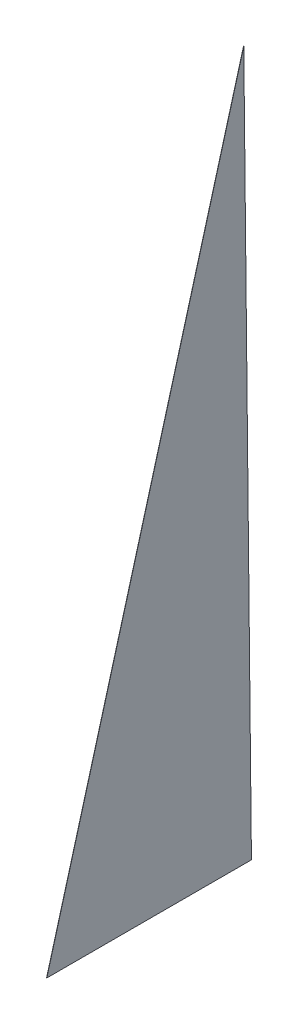
SolidWorks part; units mm, degrees
material "Corrugated Paper"
ref_plane "Front Plane" through (0, 0, 0) normal (0, 0, 1) x (1, 0, 0)
ref_plane "Top Plane" through (0, 0, 0) normal (0, 1, 0) x (1, 0, 0)
ref_plane "Right Plane" through (0, 0, 0) normal (1, 0, 0) x (0, 0, -1)
sketch "Sketch1" plane through (0, 0, 0) normal (1, 0, 0) x (0, 0, -1)
  line L0 (0, 0) -> (168.45, 605.88)
  line L1 (168.45, 605.88) -> (175, 0)
  line L2 (175, 0) -> (0, 0)
  point P6 (61.0733, 548.1905)
  dimension "D1" = 175
  dimension "D2" = 605.88
  dimension "D3" = 168.45
extrude "Boss-Extrude1" add sketch "Sketch1" along normal blind 0.1984
